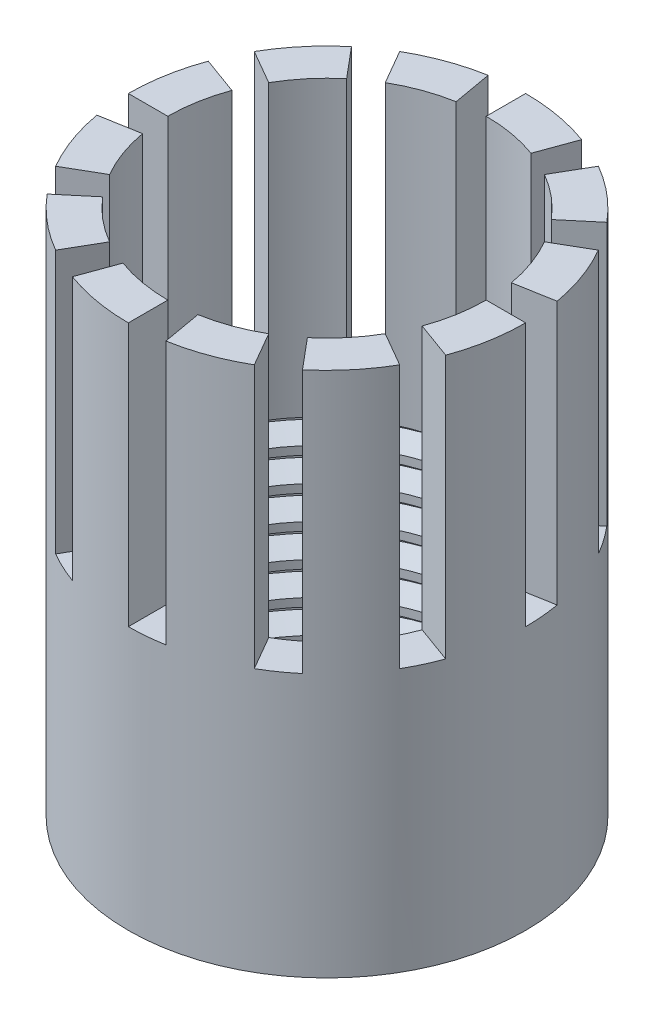
SolidWorks part; units mm, degrees
ref_plane "Front Plane" through (0, 0, 0) normal (0, 0, 1) x (1, 0, 0)
ref_plane "Top Plane" through (0, 0, 0) normal (0, 1, 0) x (1, 0, 0)
ref_plane "Right Plane" through (0, 0, 0) normal (1, 0, 0) x (0, 0, -1)
sketch "Sketch1" plane through (0, 0, 0) normal (1, 0, 0) x (0, 0, -1)
  line L0 (0, 0) -> (0, 20) construction
  line L1 (6.05, 0) -> (7.55, 0)
  line L2 (6.05, 0) -> (6.05, 20)
  line L3 (6.05, 20) -> (7.55, 20)
  line L4 (7.55, 0) -> (7.55, 20)
  point P7 (6.8, 20)
  dimension "D1" = 20
  dimension "D2" = 6.05
  dimension "D3" = 1.5
revolve "Revolve1" add sketch "Sketch1" angle 360 about L0
thread "Thread1" pitch 1.25 method cut profile "Thread Profile1" start angle 0, offset 11, length 13, pitch 1.25, diameter 12.1
ref_plane "Plane1" through (-6.05, 9, 0) normal (0, 0, 1) x (-1, 0, 0)
sketch "Thread Profile1" plane through (-6.05, 9, 0) normal (0, 0, 1) x (-1, 0, 0)
  line L0 (0, 0) -> (0, 1.25) construction
  line L1 (0, 0) -> (0.6766, 0.3906)
  line L2 (0.6766, 0.3906) -> (0.6766, 0.5469)
  line L3 (0.6766, 0.5469) -> (0, 0.9375)
  line L4 (0.6766, 0.4687) -> (0, 0.4687) construction
  line L11 (0, 0) -> (0, 0.9375)
  point P2 (0, 0)
  dimension "Pitch" = 1.25
  dimension "Profile_Angle" = 60
  dimension "Profile_Land" = 0.1562
  dimension "Profile_Height" = 0.6766
sketch "Sketch4" plane through (0, 20, 0) normal (0, 1, 0) x (1, 0, 0)
  line L0 (0, 7.55) -> (0, 0) construction
  line L1 (-1.311, 7.4353) -> (0, 0) construction
  line L2 (-1.311, 7.4353) -> (-1.0506, 5.9581)
  line L3 (0, 7.55) -> (0, 6.05)
  arc A1 (0, 7.55) -> (-1.311, 7.4353) centre (0, 0) ccw
  circle A2 centre (0, 0) radius 7.55 construction
  arc A3 (0, 6.05) -> (-1.0506, 5.9581) centre (0, 0) ccw
  circle A4 centre (0, 0) radius 6.05 construction
  dimension "D1" = 170
extrude "Cut-Extrude1" cut sketch "Sketch4" against normal blind 10
pattern_circular "CirPattern1" count 12 over 360 about axis through (0, 20, 0) along (0, -1, 0) of "Cut-Extrude1"
